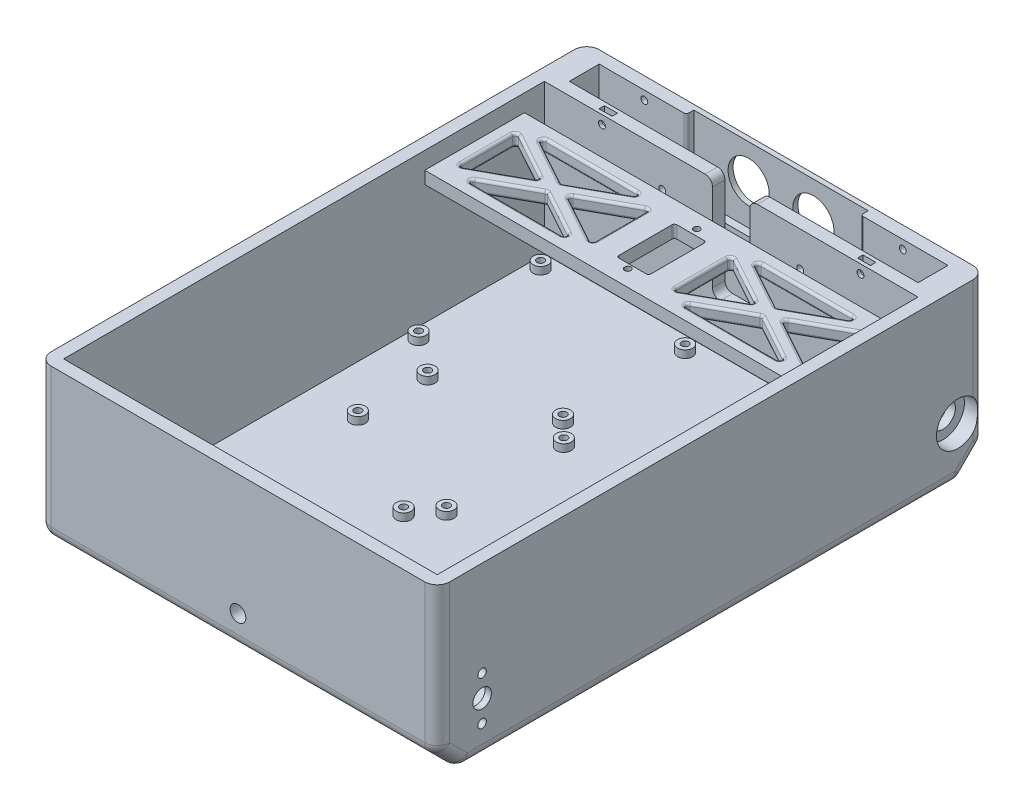
SolidWorks part; units mm, degrees
ref_plane "Front Plane" through (0, 0, 0) normal (0, 0, 1) x (1, 0, 0)
ref_plane "Top Plane" through (0, 0, 0) normal (0, 1, 0) x (1, 0, 0)
ref_plane "Right Plane" through (0, 0, 0) normal (1, 0, 0) x (0, 0, -1)
sketch "Main Body" plane through (0, 0, 0) normal (0, 1, 0) x (1, 0, 0)
  line L0 (-80, 110) -> (80, 110)
  line L1 (-75, -105) -> (75, -105)
  line L2 (-75, -105) -> (-75, 105)
  line L3 (-75, 105) -> (75, 105)
  line L4 (75, -105) -> (75, 105)
  line L5 (-75, -105) -> (75, 105) construction
  line L6 (-75, 105) -> (75, -105) construction
  line L7 (80, -110) -> (80, 110)
  line L8 (-80, -110) -> (80, -110)
  line L9 (-80, -110) -> (-80, 110)
  line L10 (-80, -110) -> (80, -110) construction
  line L11 (-80, -110) -> (-80, 110) construction
  line L12 (80, -110) -> (80, 110) construction
  line L13 (-80, 110) -> (80, 110) construction
  point P0 (0, 0)
  point P11 (0, 0)
  point P12 (0, 0)
  point P14 (0, 0)
  point P15 (0, 0)
  dimension "D1" = 75
  dimension "D2" = 210
  dimension "D3" = 5
extrude "Boss-Extrude1" add sketch "Main Body" along normal blind 8 contours L1 L4 L3 L2 | L9 L8 L7 L0 L4 L1 L2 L3 region at (0, 0, -107.2797) region at (0, 0, 0)
extrude "Boss-Extrude3" add sketch "Main Body<4>" along normal blind 60 from surface starting at face at (0, 8, 0)
sketch "Main Body<4>" plane through (0, 0, 0) normal (0, 1, 0) x (1, 0, 0) same geometry as "Main Body"
sketch "Sketch1" plane through (75, 0, 0) normal (-1, 0, 0) x (0, 0, 1)
  line L0 (105, 68) -> (105, 8) construction
  line L1 (-105, 8) -> (105, 8) construction
  line L2 (79, 15.5) -> (105, 15.5)
  line L3 (79, 8) -> (105, 8)
  line L4 (79, 8) -> (79, 34)
  line L5 (79, 34) -> (105, 34)
  line L6 (105, 8) -> (105, 34)
  line L7 (79, 8) -> (105, 34) construction
  line L8 (79, 34) -> (105, 8) construction
  circle A0 centre (92, 21) radius 13
  line M2 (-105, 8) -> (105, 8)
  line M3 (105, 8) -> (105, 68)
  dimension "D1" = 26
  dimension "D2" = 7.5
extrude "Boss-Extrude4" add sketch "Sketch1" along normal up to surface (150 mm away) contours A0 L4 M2 | A0 L3 M3 region at (75, 10.5201, 82.0674) region at (75, 10.5201, 101.9326) up to face at (-75, 38, 0)
sketch "Sketch2" plane through (0, 0, 0) normal (1, 0, 0) x (0, 0, -1)
  line L0 (-105, 68) -> (-105, 15.5) construction
  line L1 (-105, 8) -> (-79, 8)
  line L2 (-105, 8) -> (-105, 15.5)
  line L3 (-105, 15.5) -> (-79, 15.5)
  line L4 (-79, 8) -> (-79, 15.5)
  line L5 (105, 8) -> (-79, 8) construction
  line L6 (-79, 8) -> (-79, 15.5) construction
  line L7 (-79, 15.5) -> (-80.2208, 15.5) construction
extrude "Cut-Extrude1" cut sketch "Sketch2" against normal mid plane 12
sketch "Sketch3" plane through (0, 8, 0) normal (0, 1, 0) x (1, 0, 0)
  line L0 (75, -105) -> (-75, -105) construction
  line L1 (-4.5, -79) -> (-10, -79)
  line L2 (-4.5, -79) -> (-4.5, -105)
  line L3 (-4.5, -105) -> (-10, -105)
  line L4 (-10, -79) -> (-10, -105)
  line L5 (0, 0) -> (0, -105) construction
  line L6 (-75, -79) -> (-6, -79) construction
  line L7 (10, -79) -> (10, -105)
  line L8 (4.5, -105) -> (10, -105)
  line L9 (4.5, -79) -> (4.5, -105)
  line L10 (4.5, -79) -> (10, -79)
  line L11 (-6, -103.7792) -> (-6, -92) construction
  dimension "D1" = 4
  dimension "D2" = 4.5
extrude "Boss-Extrude5" add sketch "Sketch3" along normal blind 20
sketch "Sketch4" plane through (0, 8, 0) normal (0, 1, 0) x (1, 0, 0)
  line L0 (-75, -105) -> (-75, 105) construction
  line L1 (-75, 93) -> (75, 93)
  line L2 (-75, 93) -> (-75, 88)
  line L3 (-75, 88) -> (75, 88)
  line L4 (75, 93) -> (75, 88)
  line L5 (75, 105) -> (75, -105) construction
  line L6 (-75, 105) -> (75, 105) construction
  line L8 (-75, 93) -> (-70, 93)
  line L9 (-75, 93) -> (-75, 105)
  line L10 (-75, 105) -> (-70, 105)
  line L11 (-70, 93) -> (-70, 105)
  line L12 (75, 93) -> (70, 93)
  line L13 (75, 93) -> (75, 105)
  line L14 (75, 105) -> (70, 105)
  line L15 (70, 93) -> (70, 105)
  line M9 (75, -79) -> (75, 105)
  line M10 (75, 105) -> (-75, 105)
  line M11 (-75, 105) -> (-75, -79)
  dimension "D1" = 17
  dimension "D2" = 5
  dimension "D3" = 5
extrude "Boss-Extrude6" add sketch "Sketch4" along normal up to surface (60 mm away) contours L3 L1 M11 M9 | L15 L1 M9 M10 | L8 L11 L10 L9 region at (0, 8, -90.5) region at (72.5, 8, -99) up to face at (0, 68, 0)
sketch "Sketch5" plane through (80, 0, 0) normal (1, 0, 0) x (0, 0, -1)
  circle A0 centre (-92, 21) radius 3.5 construction
  circle A1 centre (-92, 21) radius 3.5
  circle A2 centre (-92, 21) radius 3.7
  dimension "D1" = 0.2
extrude "Cut-Extrude4" cut sketch "Sketch5" against normal up to next contours A1 | A2 A1 region at (80, 21, 92) region at (80, 21, 95.5953)
sketch "Sketch6" plane through (-75, 0, 0) normal (1, 0, 0) x (0, 0, -1)
  circle A0 centre (-92, 21) radius 13
  dimension "D1" = 26
extrude "Cut-Extrude5" cut sketch "Sketch6" against normal offset from surface (2.5 mm away) 2.5 up to face at (-80, 34, 0)
mirror "Mirror1" about plane through (0, 0, 0) normal (1, 0, 0) of "Cut-Extrude4"
sketch "Sketch8" plane through (75, 0, 0) normal (-1, 0, 0) x (0, 0, 1)
  circle A0 centre (92, 21) radius 13
  dimension "D1" = 26
extrude "Cut-Extrude6" cut sketch "Sketch8" against normal offset from surface (2.5 mm away) 2.5 up to face at (80, 21, 88.3)
sketch "Sketch10" plane through (80, 0, 0) normal (1, 0, 0) x (0, 0, -1)
  circle A1 centre (-92, 12.25) radius 1.25
  circle A2 centre (-92, 12.25) radius 1.25
  circle A3 centre (-92, 29.75) radius 1.25
  circle A4 centre (-92, 29.75) radius 1.25
  circle A5 centre (-92, 21) radius 12.5
  circle A6 centre (-92, 21) radius 12.5
  circle A63 centre (-92, 29.75) radius 1.7
  circle A64 centre (-92, 12.25) radius 1.7
  dimension "D4" = 3.4
  dimension "D1" = 0
  dimension "D2" = 0
  dimension "D3" = 0
extrude "Cut-Extrude7" cut sketch "Sketch10" against normal up to next contours A2 | A64 A2 | A4 | A63 A4 region at (80, 12.25, 92) region at (80, 29.75, 92) region at (80, 29.75, 93.6519) region at (80, 12.25, 93.6519)
mirror "Mirror3" about plane through (0, 0, 0) normal (1, 0, 0) of "Cut-Extrude7"
sketch "Sketch14" plane through (0, 8, 0) normal (0, 1, 0) x (1, 0, 0)
  line L0 (-4.5, -105) -> (-4.5, -79) construction
  line L1 (-4.5, -95) -> (4.5, -95)
  line L2 (-4.5, -95) -> (-4.5, -105)
  line L3 (-4.5, -105) -> (4.5, -105)
  line L4 (4.5, -95) -> (4.5, -105)
  dimension "D1" = 10
extrude "Boss-Extrude9" add sketch "Sketch14" along normal blind 5
sketch "Sketch15" plane through (0, 0, 110) normal (0, 0, 1) x (1, 0, 0)
  arc A4 (3.15, 19.5) -> (-3.15, 19.5) centre (0, 19.5) ccw
  arc A5 (-3.15, 19.5) -> (3.15, 19.5) centre (0, 19.5) ccw
  circle A7 centre (0, 19.5) radius 3 construction
  dimension "D1" = 3.15
extrude "Cut-Extrude12" cut sketch "Sketch15" against normal up to next contours A4 A5 region at (0, 19.5, 110)
sketch "Sketch16" plane through (0, 0, 0) normal (0, -1, 0) x (1, 0, 0)
  circle A0 centre (-12.5, -82) radius 1.475 construction
  circle A1 centre (-70.5, -82) radius 1.475 construction
  circle A2 centre (-70.5, -33) radius 1.475 construction
  circle A3 centre (-12.5, -33) radius 1.475 construction
  circle A4 centre (-4.2, -25) radius 1.475 construction
  circle A5 centre (-55, -21.12) radius 1.475 construction
  circle A6 centre (-55, 6.88) radius 1.475 construction
  circle A7 centre (-4.2, 22.08) radius 1.475 construction
  circle A8 centre (-12.3, 31.18) radius 1.475 construction
  circle A9 centre (24.2, 31.18) radius 1.475 construction
  circle A10 centre (37.8459, 24.117) radius 1.475 construction
  circle A11 centre (59.5541, 24.117) radius 1.475 construction
  circle A12 centre (59.5541, 68.243) radius 1.475 construction
  circle A13 centre (37.8459, 68.243) radius 1.475 construction
  circle A14 centre (24.2, 67.68) radius 1.475 construction
  circle A15 centre (-12.3, 67.68) radius 1.475 construction
  circle A16 centre (-12.5, -82) radius 1.475
  circle A17 centre (-70.5, -82) radius 1.475
  circle A18 centre (-70.5, -33) radius 1.475
  circle A19 centre (-12.5, -33) radius 1.475
  circle A20 centre (-4.2, -25) radius 1.475
  circle A21 centre (-55, -21.12) radius 1.475
  circle A22 centre (-55, 6.88) radius 1.475
  circle A23 centre (-4.2, 22.08) radius 1.475
  circle A24 centre (-12.3, 31.18) radius 1.475
  circle A25 centre (24.2, 31.18) radius 1.475
  circle A26 centre (37.8459, 24.117) radius 1.475
  circle A27 centre (59.5541, 24.117) radius 1.475
  circle A28 centre (59.5541, 68.243) radius 1.475
  circle A29 centre (37.8459, 68.243) radius 1.475
  circle A30 centre (24.2, 67.68) radius 1.475
  circle A31 centre (-12.3, 67.68) radius 1.475
  circle A32 centre (-70.5, -82) radius 1.45
  circle A33 centre (-12.5, -82) radius 1.45
  circle A34 centre (-12.5, -33) radius 1.45
  circle A35 centre (-4.2, -25) radius 1.45
  circle A36 centre (-55, -21.12) radius 1.45
  circle A37 centre (-70.5, -33) radius 1.45
  circle A38 centre (-55, 6.88) radius 1.45
  circle A39 centre (-12.3, 31.18) radius 1.45
  circle A40 centre (-4.2, 22.08) radius 1.45
  circle A41 centre (24.2, 31.18) radius 1.45
  circle A42 centre (37.8459, 24.117) radius 1.45
  circle A43 centre (59.5541, 24.117) radius 1.45
  circle A44 centre (37.8459, 68.243) radius 1.45
  circle A45 centre (59.5541, 68.243) radius 1.45
  circle A46 centre (24.2, 67.68) radius 1.45
  circle A47 centre (-12.3, 67.68) radius 1.45
  dimension "D1" = 2.9
extrude "Cut-Extrude13" cut sketch "Sketch16" against normal up to next contours A47 | A46 | A44 | A45 | A35 | A37 | A36 | A38 | A39 | A40 | A41 | A42 | A43 | A32 | A33 | A19 region at (-70.5, 0, -82) region at (-12.5, 0, -82) region at (-4.2, 0, -25) region at (-55, 0, -21.12) region at (-70.5, 0, -33) region at (-55, 0, 6.88) region at (-12.3, 0, 31.18) region at (-4.2, 0, 22.08) region at (24.2, 0, 31.18) region at (37.8459, 0, 24.117) region at (59.5541, 0, 24.117) region at (37.8459, 0, 68.243) region at (59.5541, 0, 68.243) region at (24.2, 0, 67.68) region at (-12.3, 0, 67.68)
sketch "Sketch18" plane through (75, 0, 0) normal (-1, 0, 0) x (0, 0, 1)
  line L0 (-110, 68) -> (-110, 0) construction
  line L1 (-80, 61.1) -> (-40, 61.1)
  line L2 (-80, 61.1) -> (-80, 56.1)
  line L3 (-80, 56.1) -> (-40, 56.1)
  line L4 (-40, 61.1) -> (-40, 56.1)
  line L5 (-88, 68) -> (105, 68) construction
  dimension "D1" = 5
  dimension "D2" = 30
  dimension "D3" = 40
  dimension "D4" = 6.9
extrude "Boss-Extrude11" add sketch "Sketch18" along normal up to next
sketch "Sketch19" plane through (0, 68, 0) normal (0, 1, 0) x (1, 0, 0)
  line L1 (-6.425, 71.625) -> (6.425, 71.625)
  line L2 (-6.425, 71.625) -> (-6.425, 48.375)
  line L3 (-6.425, 48.375) -> (6.425, 48.375)
  line L4 (6.425, 71.625) -> (6.425, 48.375)
  line L12 (-75, 80) -> (-75, 40)
  line L13 (-75, 40) -> (75, 40)
  line L14 (75, 40) -> (75, 80)
  line L15 (75, 80) -> (-75, 80)
  line L16 (-75, 80) -> (-75, 40)
  line L17 (-75, 40) -> (75, 40)
  line L18 (75, 40) -> (75, 80)
  line L19 (75, 80) -> (-75, 80)
  point P4 (0, 71.625)
  point P8 (0, 80)
  point P12 (6.425, 60)
  point P13 (75, 60)
  dimension "D1" = 23.25
  dimension "D2" = 12.85
  dimension "D3" = 0
extrude "Cut-Extrude14" cut sketch "Sketch19" against normal up to next contours L4 L1 L2 L3 region at (0, 68, -60)
sketch "Sketch21" plane through (0, 0, -110) normal (0, 0, -1) x (-1, 0, 0)
  circle A1 centre (-51.875, 64.5) radius 1.375
  circle A2 centre (-51.875, 64.5) radius 1.375
  circle A3 centre (51.875, 64.5) radius 1.375
  circle A4 centre (51.875, 64.5) radius 1.375
  circle A44 centre (-51.875, 64.5) radius 1.375
  circle A45 centre (51.875, 64.5) radius 1.375
  dimension "D3" = 2.75
extrude "Cut-Extrude16" cut sketch "Sketch21" against normal up to surface (22 mm away) contours A2 | A4 region at (51.875, 64.5, -110) region at (-51.875, 64.5, -110) up to face at (0, 38, -88)
ref_plane "Plane1" through (0, 0, -90.5) normal (0, 0, -1) x (-1, 0, 0)
sketch "Sketch22" plane through (0, 0, -90.5) normal (0, 0, -1) x (-1, 0, 0)
  line L0 (-54.475, 66.0011) -> (-54.475, 68)
  line L1 (-49.275, 66.0011) -> (-51.875, 67.5022)
  line L2 (-51.875, 67.5022) -> (-54.475, 66.0011)
  line L3 (-54.475, 66.0011) -> (-54.475, 62.9989)
  line L4 (-54.475, 62.9989) -> (-51.875, 61.4978)
  line L5 (-51.875, 61.4978) -> (-49.275, 62.9989)
  line L6 (-49.275, 62.9989) -> (-49.275, 66.0011)
  line L7 (-54.475, 68) -> (-49.275, 68)
  line L8 (-49.275, 68) -> (-49.275, 66.0011)
  line L9 (-75, 68) -> (75, 68) construction
  line L10 (0, 0) -> (0, 68) construction
  line L11 (80, 68) -> (-80, 68) construction
  line L12 (51.875, 61.4978) -> (49.275, 62.9989)
  line L13 (54.475, 62.9989) -> (51.875, 61.4978)
  line L14 (51.875, 67.5022) -> (54.475, 66.0011)
  line L15 (54.475, 66.0011) -> (54.475, 62.9989)
  line L16 (54.475, 66.0011) -> (54.475, 68)
  line L17 (49.275, 62.9989) -> (49.275, 66.0011)
  line L18 (49.275, 68) -> (49.275, 66.0011)
  line L19 (54.475, 68) -> (49.275, 68)
  line L20 (49.275, 66.0011) -> (51.875, 67.5022)
  circle A0 centre (-51.875, 64.5) radius 2.6 construction
  circle A3 centre (-51.875, 64.5) radius 1.375 construction
  dimension "D1" = 5.2
extrude "Cut-Extrude17" cut sketch "Sketch22" against normal mid plane 2.2 contours L20 L17 L12 L13 L15 L14 | L18 L20 L14 L16 L19 | L5 L6 L1 L2 L3 L4 | L8 L7 L0 L2 L1 region at (54.4193, 67.0006, -90.5) region at (51.875, 64.5, -90.5) region at (-51.875, 64.5, -90.5) region at (-49.3307, 67.0006, -90.5)
sketch "Sketch23" plane through (0, 0, -110) normal (0, 0, -1) x (-1, 0, 0)
  circle A0 centre (51.875, 64.5) radius 2.5
  circle A1 centre (-51.875, 64.5) radius 2.5
  circle A6 centre (-51.875, 64.5) radius 1.375 construction
  circle A7 centre (51.875, 64.5) radius 1.375 construction
  dimension "D1" = 5
  dimension "D2" = 5
extrude "Cut-Extrude18" cut sketch "Sketch23" against normal mid plane 2.5
sketch "Sketch24" plane through (0, 61.1, 0) normal (0, 1, 0) x (1, 0, 0)
  circle A0 centre (0, 46.475) radius 1.2502
  arc A1 (0.4, 45.5583) -> (-0.4, 45.5583) centre (0, 46.475) ccw construction
  circle A2 centre (0, 74.175) radius 1.2502
  arc A3 (-0.4, 75.0917) -> (0, 73.1748) centre (0, 74.175) ccw construction
  point P5 (0.4, 45.5583)
  dimension "D1" = 0.25
extrude "Cut-Extrude19" cut sketch "Sketch24" against normal up to next
sketch "Sketch25" plane through (0, 61.1, 0) normal (0, 1, 0) x (1, 0, 0)
  line L1 (-11.3, 80) -> (11.3, 80)
  line L2 (-11.3, 80) -> (-11.3, 40)
  line L3 (-11.3, 40) -> (11.3, 40)
  line L4 (-75, 80) -> (-75, 40)
  line L5 (-75, 40) -> (75, 40)
  line L6 (75, 40) -> (75, 80)
  line L7 (75, 80) -> (-75, 80)
  line L8 (-75, 80) -> (-75, 40)
  line L9 (-75, 40) -> (75, 40)
  line L10 (75, 40) -> (75, 80)
  line L11 (75, 80) -> (-75, 80)
  line L12 (11.3, 80) -> (11.3, 40)
  line L13 (-11.3, 80) -> (11.3, 40) construction
  line L14 (-11.3, 40) -> (11.3, 80) construction
  line L15 (0, 80) -> (0, 40) construction
  line L16 (70, 75) -> (70, 45)
  line L17 (-70, 75) -> (-16.3, 75)
  line L18 (-70, 75) -> (-70, 45)
  line L19 (-70, 45) -> (-16.3, 45)
  line L20 (-16.3, 75) -> (-16.3, 45)
  line L21 (-70, 75) -> (-16.3, 45) construction
  line L22 (-70, 45) -> (-16.3, 75) construction
  line L23 (70, 75) -> (16.3, 45) construction
  line L24 (70, 45) -> (16.3, 75) construction
  line L25 (70, 75) -> (16.3, 75)
  line L26 (16.3, 75) -> (16.3, 45)
  line L27 (70, 45) -> (16.3, 45)
  line L28 (-75, 60) -> (-11.3, 60) construction
  line L29 (75, 60) -> (11.3, 60) construction
  line L30 (-70, 71.9362) -> (-48.3314, 60)
  line L31 (-16.3, 71.9362) -> (-37.9686, 60)
  line L32 (70, 71.9362) -> (48.3314, 60)
  line L33 (-48.3314, 60) -> (-70, 48.0638)
  line L34 (48.3314, 60) -> (70, 48.0638)
  line L35 (-65.199, 45) -> (-43.15, 57.1458)
  line L36 (65.199, 45) -> (43.15, 57.1458)
  line L37 (-43.15, 57.1458) -> (-21.101, 45)
  line L38 (43.15, 57.1458) -> (21.101, 45)
  line L39 (16.3, 71.9362) -> (37.9686, 60)
  line L40 (-37.9686, 60) -> (-16.3, 48.0638)
  line L41 (37.9686, 60) -> (16.3, 48.0638)
  line L42 (-65.199, 75) -> (-43.15, 62.8542)
  line L43 (65.199, 75) -> (43.15, 62.8542)
  line L44 (-43.15, 62.8542) -> (-21.101, 75)
  line L45 (43.15, 62.8542) -> (21.101, 75)
  line L46 (-75, 40) -> (-75, 80) construction
  line L47 (-75, 40) -> (75, 40) construction
  point P2 (0, 60)
  point P9 (-43.15, 60)
  point P10 (75, 60)
  point P24 (43.15, 60)
  point P62 (-54.1745, 68.9271)
  dimension "D2" = 150
  dimension "D3" = 5
  dimension "D4" = 5
  dimension "D5" = 5
  dimension "D6" = 26.6686
  dimension "D7" = 140.199
  dimension "D1" = 0
extrude "Cut-Extrude21" cut sketch "Sketch25" against normal up to next contours L37 L35 L19 | L33 L30 L18 | L42 L44 L17 | L31 L40 L20 | L41 L39 L26 | L45 L43 L25 | L36 L38 L27 | L32 L34 L16 region at (62.7771, 61.1, -60) region at (43.15, 61.1, -70.9514) region at (43.15, 61.1, -49.0486) region at (23.5229, 61.1, -60) region at (-43.15, 61.1, -70.9514) region at (-62.7771, 61.1, -60) region at (-23.5229, 61.1, -60) region at (-43.15, 61.1, -49.0486)
fillet "Fillet2" radius 1 76 edges at (-32.1255, 56.1, -51.0729) (-32.1255, 61.1, -51.0729) (-21.101, 58.6, -45) (-43.15, 61.1, -45) (-43.15, 56.1, -45) (-54.1745, 56.1, -51.0729) (-65.199, 58.6, -45) (-54.1745, 61.1, -51.0729) (-43.15, 58.6, -57.1458) (32.1255, 56.1, -68.9271) (32.1255, 61.1, -68.9271) (21.101, 58.6, -75) (43.15, 61.1, -75) (43.15, 56.1, -75) (54.1745, 56.1, -68.9271) (65.199, 58.6, -75) (54.1745, 61.1, -68.9271) (43.15, 58.6, -62.8542) (54.1745, 61.1, -51.0729) (54.1745, 56.1, -51.0729) (43.15, 56.1, -45) (65.199, 58.6, -45) (43.15, 61.1, -45) (21.101, 58.6, -45) (32.1255, 61.1, -51.0729) (43.15, 58.6, -57.1458) (32.1255, 56.1, -51.0729) (59.1657, 61.1, -65.9681) (59.1657, 56.1, -65.9681) (70, 56.1, -60) (70, 58.6, -71.9362) (70, 61.1, -60) (70, 58.6, -48.0638) (59.1657, 61.1, -54.0319) (48.3314, 58.6, -60) (59.1657, 56.1, -54.0319) (-54.1745, 61.1, -68.9271) (-54.1745, 56.1, -68.9271) (-43.15, 56.1, -75) (-65.199, 58.6, -75) (-43.15, 61.1, -75) (-21.101, 58.6, -75) (-32.1255, 61.1, -68.9271) (-43.15, 58.6, -62.8542) (-32.1255, 56.1, -68.9271) (-59.1657, 56.1, -54.0319) (-59.1657, 61.1, -54.0319) (-70, 58.6, -48.0638) (-70, 61.1, -60) (-70, 56.1, -60) (-59.1657, 56.1, -65.9681) (-70, 58.6, -71.9362) (-59.1657, 61.1, -65.9681) (-48.3314, 58.6, -60) (-27.1343, 61.1, -65.9681) (-27.1343, 56.1, -65.9681) (-16.3, 56.1, -60) (-16.3, 58.6, -71.9362) (-16.3, 61.1, -60) (-16.3, 58.6, -48.0638) (-27.1343, 61.1, -54.0319) (-37.9686, 58.6, -60) (-27.1343, 56.1, -54.0319) (27.1343, 56.1, -54.0319) (27.1343, 61.1, -54.0319) (16.3, 58.6, -48.0638) (16.3, 61.1, -60) (16.3, 56.1, -60) (27.1343, 56.1, -65.9681) (16.3, 58.6, -71.9362) (27.1343, 61.1, -65.9681) (37.9686, 58.6, -60) (6.425, 58.6, -48.375) (-6.425, 58.6, -48.375) (-6.425, 58.6, -71.625) (6.425, 58.6, -71.625)
sketch "Sketch33" plane through (0, 0, -110) normal (0, 0, -1) x (-1, 0, 0)
  circle A0 centre (-13, 53.9999) radius 8.25
  circle A1 centre (13, 53.9999) radius 8.25
  circle A2 centre (-13, 53.9999) radius 7.3 construction
  circle A3 centre (13, 53.9999) radius 7.3 construction
  dimension "D1" = 16.5
extrude "Cut-Extrude27" cut sketch "Sketch33" against normal up to next
sketch "Sketch34" plane through (0, 0, -93) normal (0, 0, -1) x (-1, 0, 0)
  circle A0 centre (27.7, 54) radius 1.35 construction
  circle A1 centre (27.7, 54) radius 1.35
  circle A2 centre (-27.7, 54) radius 1.35 construction
  circle A3 centre (-27.7, 54) radius 1.35
  circle A4 centre (-27.7, 54) radius 1.375
  circle A5 centre (27.7, 54) radius 1.375
  dimension "D1" = 2.75
  dimension "D2" = 2.75
extrude "Cut-Extrude28" cut sketch "Sketch34" against normal up to next contours A4 A3 | A1 | A5 A1 | A3 region at (-27.7, 54, -93) region at (29.0711, 54, -93) region at (-26.3289, 54, -93)
sketch "Sketch35" plane through (0, 68, 0) normal (0, 1, 0) x (1, 0, 0)
  line L0 (70, 93) -> (-70, 93) construction
  line L1 (-7.5, 93) -> (7.5, 93)
  line L2 (-7.5, 93) -> (-7.5, 88)
  line L3 (-7.5, 88) -> (7.5, 88)
  line L4 (7.5, 93) -> (7.5, 88)
  line L5 (-7.5, 93) -> (7.5, 88) construction
  line L6 (-7.5, 88) -> (7.5, 93) construction
  line L7 (-75, 88) -> (75, 88) construction
  point P0 (0, 90.5)
  dimension "D1" = 15
extrude "Cut-Extrude29" cut sketch "Sketch35" against normal offset from surface (41 mm away) 19 up to face at (-4.2, 8, -23.55)
fillet "Fillet4" radius 3 9 edges at (0, 8, 95) (-7.25, 28, 79) (-7.25, 28, 105) (7.25, 28, 105) (7.25, 28, 79) (-7.5, 68, -90.5) (7.5, 68, -90.5) (-7.5, 27, -90.5) (7.5, 27, -90.5)
fillet "Fillet5" radius 1 1 edges at (0, 13, 95)
sketch "Sketch36" plane through (0, 68, 0) normal (0, 1, 0) x (1, 0, 0)
  line L0 (-70, 105) -> (70, 105) construction
  line L1 (-35, 108) -> (35, 108)
  line L2 (-35, 108) -> (-35, 105)
  line L3 (-35, 105) -> (35, 105)
  line L4 (35, 108) -> (35, 105)
  line L5 (-80, 110) -> (80, 110) construction
  point P6 (0, 108)
  dimension "D1" = 70
  dimension "D2" = 2
extrude "Cut-Extrude30" cut sketch "Sketch36" against normal blind 30
fillet "Fillet6" radius 1 2 edges at (35, 53, -105) (-35, 53, -105)
sketch "Sketch37" plane through (0, 8, 0) normal (0, 1, 0) x (1, 0, 0)
  line L8 (-4.5, -79) -> (-4.5, -92)
  line L9 (-4.5, -92) -> (4.5, -92)
  line L10 (4.5, -92) -> (4.5, -79)
  line L11 (4.5, -79) -> (75, -79)
  line L12 (75, -79) -> (75, 88)
  line L13 (75, 88) -> (-75, 88)
  line L14 (-75, 88) -> (-75, -79)
  line L15 (-75, -79) -> (-4.5, -79)
  line L16 (-4.5, -79) -> (-4.5, -92)
  line L17 (-4.5, -92) -> (4.5, -92)
  line L18 (4.5, -92) -> (4.5, -79)
  line L19 (4.5, -79) -> (75, -79)
  line L20 (75, -79) -> (75, 88)
  line L22 (-75, 88) -> (-75, -79)
  line L23 (-75, -79) -> (-4.5, -79)
  line L29 (75, 88) -> (-75, 88)
  circle A0 centre (-12.5, 82) radius 1.45 construction
  circle A1 centre (-4.2, 25) radius 1.45 construction
  circle A2 centre (-12.5, 33) radius 1.475 construction
  circle A3 centre (-70.5, 33) radius 1.45 construction
  circle A4 centre (-55, 21.12) radius 1.45 construction
  circle A5 centre (-55, -6.88) radius 1.45 construction
  circle A6 centre (-12.3, -31.18) radius 1.45 construction
  circle A7 centre (-4.2, -22.08) radius 1.45 construction
  circle A8 centre (24.2, -31.18) radius 1.45 construction
  circle A9 centre (37.8459, -24.117) radius 1.45 construction
  circle A10 centre (59.5541, -24.117) radius 1.45 construction
  circle A11 centre (59.5541, -68.243) radius 1.45 construction
  circle A12 centre (37.8459, -68.243) radius 1.45 construction
  circle A13 centre (24.2, -67.68) radius 1.45 construction
  circle A14 centre (-12.3, -67.68) radius 1.45 construction
  circle A15 centre (-70.5, 82) radius 1.45 construction
  circle A16 centre (-12.5, 82) radius 1.45
  circle A17 centre (-4.2, 25) radius 1.45
  circle A18 centre (-12.5, 33) radius 1.475
  circle A19 centre (-70.5, 33) radius 1.45
  circle A20 centre (-55, 21.12) radius 1.45
  circle A21 centre (-55, -6.88) radius 1.45
  circle A22 centre (-12.3, -31.18) radius 1.45
  circle A23 centre (-4.2, -22.08) radius 1.45
  circle A24 centre (24.2, -31.18) radius 1.45
  circle A25 centre (37.8459, -24.117) radius 1.45
  circle A26 centre (59.5541, -24.117) radius 1.45
  circle A27 centre (59.5541, -68.243) radius 1.45
  circle A28 centre (37.8459, -68.243) radius 1.45
  circle A29 centre (24.2, -67.68) radius 1.45
  circle A30 centre (-12.3, -67.68) radius 1.45
  circle A31 centre (-70.5, 82) radius 1.45
  circle A32 centre (-12.3, -67.68) radius 3
  circle A33 centre (24.2, -67.68) radius 3
  circle A34 centre (37.8459, -68.243) radius 3
  circle A35 centre (59.5541, -68.243) radius 3
  circle A36 centre (24.2, -31.18) radius 3
  circle A37 centre (37.8459, -24.117) radius 3
  circle A38 centre (59.5541, -24.117) radius 3
  circle A39 centre (-4.2, -22.08) radius 3
  circle A40 centre (-12.3, -31.18) radius 3
  circle A41 centre (-4.2, 25) radius 3
  circle A42 centre (-55, -6.88) radius 3
  circle A43 centre (-55, 21.12) radius 3
  circle A44 centre (-12.5, 33) radius 3
  circle A45 centre (-12.5, 82) radius 3
  circle A46 centre (-70.5, 82) radius 3
  circle A47 centre (-70.5, 33) radius 3
  circle M9 centre (-4.2, 25) radius 1.45
  circle M10 centre (59.5541, -68.243) radius 1.45
  circle M11 centre (37.8459, -68.243) radius 1.45
  circle M12 centre (24.2, -67.68) radius 1.45
  circle M13 centre (-70.5, 33) radius 1.45
  circle M14 centre (-55, 21.12) radius 1.45
  circle M15 centre (-55, -6.88) radius 1.45
  circle M16 centre (-12.3, -31.18) radius 1.45
  circle M17 centre (-4.2, -22.08) radius 1.45
  circle M18 centre (24.2, -31.18) radius 1.45
  circle M19 centre (37.8459, -24.117) radius 1.45
  circle M20 centre (59.5541, -24.117) radius 1.45
  circle M21 centre (-70.5, 82) radius 1.45
  circle M22 centre (-12.5, 82) radius 1.45
  circle M23 centre (-12.5, 33) radius 1.475
  circle M24 centre (-12.3, -67.68) radius 1.45
  dimension "D2" = 6
  dimension "D1" = 0
extrude "Boss-Extrude12" add sketch "Sketch37" along normal blind 3 contours A46 M21 | A45 M22 | A44 M23 | A41 M9 | A47 M13 | A43 M14 | A42 M15 | A38 M20 | A35 M10 | A34 M11 | A37 M19 | A36 M18 | A33 M12 | A39 M17 | A40 M16 | A32 M24 region at (-15.2151, 8, 67.68) region at (21.2849, 8, 67.68) region at (34.9307, 8, 68.243) region at (56.639, 8, 68.243) region at (21.2849, 8, 31.18) region at (34.9307, 8, 24.117) region at (56.639, 8, 24.117) region at (-7.1151, 8, 22.08) region at (-15.2151, 8, 31.18) region at (-7.1151, 8, -25) region at (-57.9151, 8, 6.88) region at (-57.9151, 8, -21.12) region at (-15.4151, 8, -33) region at (-15.4151, 8, -82) region at (-73.4151, 8, -82) region at (-73.4151, 8, -33)
sketch "Sketch38" plane through (80, 0, 0) normal (1, 0, 0) x (0, 0, -1)
  line L0 (93, 68) -> (105, 68) construction
  line L1 (93, 68) -> (105, 68) construction
  circle A0 centre (99, 21) radius 8.625
  circle A1 centre (-92, 21) radius 3.7 construction
  circle A2 centre (-92, 21) radius 3.7 construction
  point P2 (0, 0)
  point P6 (0, 0)
  point P9 (99, 68)
  dimension "D1" = 17.25
extrude "Cut-Extrude31" cut sketch "Sketch38" against normal blind 6 contours A0 region at (80, 21, -99)
sketch "Sketch39" plane through (74, 0, 0) normal (1, 0, 0) x (0, 0, -1)
  circle A0 centre (99, 21) radius 5
  circle A1 centre (99, 21) radius 8.625 construction
  point P4 (0, 0)
  dimension "D1" = 10
extrude "Cut-Extrude32" cut sketch "Sketch39" against normal blind 3.5
mirror "Mirror7" about plane through (0, 0, 0) normal (1, 0, 0) of "Cut-Extrude31", "Cut-Extrude32"
chamfer "Chamfer1" distance 10 angle 45 2 edges at (0, 0, 110) (0, 0, -110)
fillet "Fillet7" radius 5 14 edges at (0, 10, 110) (80, 5, 105) (0, 0, 100) (-80, 5, 105) (0, 0, -100) (80, 5, -105) (0, 10, -110) (-80, 5, -105) (80, 39, 110) (-80, 39, 110) (-80, 0, 0) (80, 0, 0) (80, 39, -110) (-80, 39, -110)
equation "\"Screw\"=2.75"
equation "\"D1@Sketch16\"=\"Mount\""
equation "\"D3@Sketch21\"=\"Screw\""
equation "\"D2@Sketch34\"=\"Screw\""
equation "\"D1@Sketch34\"=\"Screw\""
equation "\"Mount\"= 2.9"
